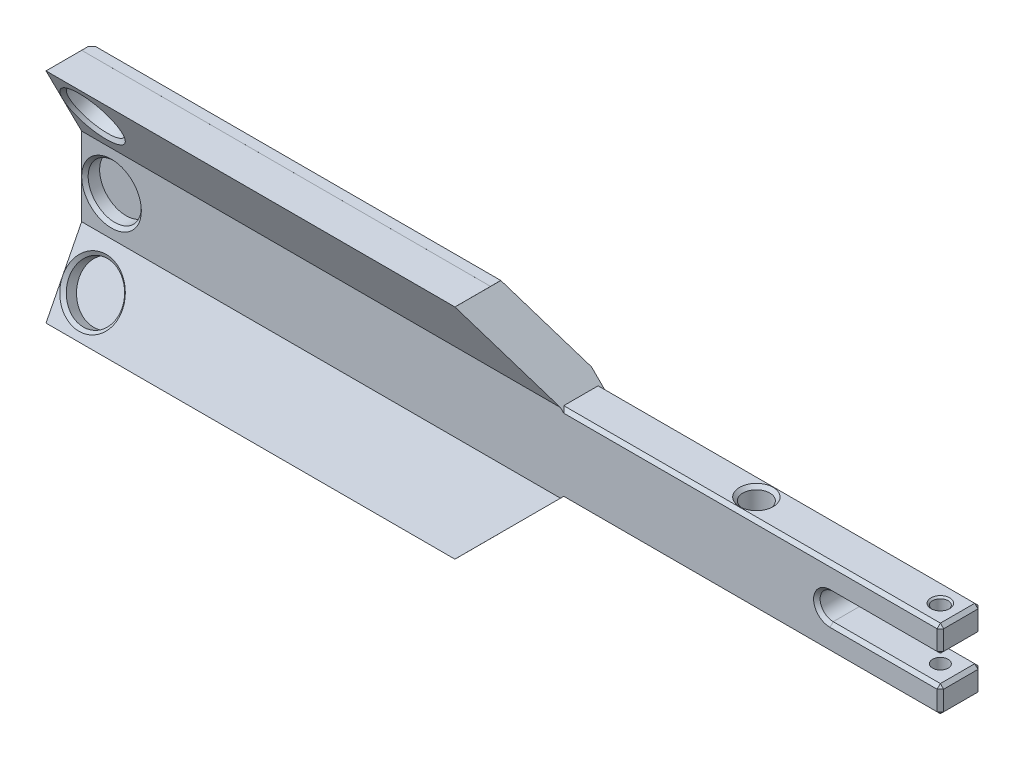
SolidWorks part; units mm, degrees
ref_plane "Front" through (0, 0, 0) normal (0, 0, 1) x (1, 0, 0)
ref_plane "Top" through (0, 0, 0) normal (0, 1, 0) x (1, 0, 0)
ref_plane "Right" through (0, 0, 0) normal (1, 0, 0) x (0, 0, -1)
sketch "Sketch1" plane through (0, 0, 0) normal (0, 0, 1) x (1, 0, 0)
  line L1 (52.5, -4.8) -> (-52.5, -4.8)
  line L2 (52.5, -4.8) -> (52.5, 4.8)
  line L3 (52.5, 4.8) -> (-52.5, 4.8)
  line L4 (-52.5, -4.8) -> (-52.5, 4.8)
  line L5 (52.5, -4.8) -> (-52.5, 4.8) construction
  line L6 (52.5, 4.8) -> (-52.5, -4.8) construction
  point P0 (0, 0)
  dimension "D1" = 9.6
  dimension "D2" = 105
extrude "Boss-Extrude1" add sketch "Sketch1" along normal blind 5
sketch "Sketch2" plane through (0, 4.8, 0) normal (0, 1, 0) x (1, 0, 0)
  line L0 (52.5, -5) -> (52.5, 0) construction
  line L2 (52.5, 0) -> (-52.5, 0) construction
  circle A0 centre (27.5, -2.5) radius 1.65
  dimension "D3" = 3.3
  dimension "D1" = 2.5
  dimension "D2" = 25
sketch "Sketch4" plane through (0, 0, 5) normal (0, 0, 1) x (1, 0, 0)
  line L0 (39, 0) -> (45, 0) construction
  line L1 (39, 1.6) -> (45, 1.6)
  line L2 (39, -1.6) -> (45, -1.6)
  arc A0 (39, 1.6) -> (39, -1.6) centre (39, 0) ccw
  arc A1 (45, -1.6) -> (45, 1.6) centre (45, 0) ccw
  point P2 (42, 0)
  dimension "D1" = 1.6
  dimension "D2" = 42
  dimension "D3" = 6
extrude "Cut-Extrude1" cut sketch "Sketch4" against normal blind 5
sketch "Sketch14" plane through (0, 0, 5) normal (0, 0, 1) x (1, 0, 0)
  line L0 (39, -1.6) -> (45, -1.6) construction
  line L1 (44.5, -1.6) -> (52.5, -1.6)
  line L2 (44.5, -1.6) -> (44.5, 1.6)
  line L3 (44.5, 1.6) -> (52.5, 1.6)
  line L4 (52.5, -1.6) -> (52.5, 1.6)
  line L5 (52.5, -4.8) -> (52.5, 4.8) construction
  line L6 (45, 1.6) -> (39, 1.6) construction
  dimension "D1" = 8
extrude "Cut-Extrude7" cut sketch "Sketch14" against normal blind 10
sketch "Sketch8" plane through (0, 0, 0) normal (0, 0, -1) x (-1, 0, 0)
  line L0 (52.5, 4.8) -> (52.5, -4.8) construction
  line L1 (52.5, 13.355) -> (2.5, 13.355)
  line L2 (52.5, 13.355) -> (52.5, -13.355)
  line L3 (52.5, -13.355) -> (2.5, -13.355)
  line L4 (2.5, 13.355) -> (2.5, -13.355)
  line L5 (2.5, 0) -> (52.5, 0) construction
  line L7 (-52.5, 0) -> (53.7381, 0) construction
  dimension "D1" = 26.71
  dimension "D3" = 50
extrude "Boss-Extrude3" add sketch "Sketch8" against normal up to surface (5 mm away) up to face at (22.675, 0, 5)
sketch "Sketch9" plane through (-52.5, 0, 0) normal (-1, 0, 0) x (0, 0, 1)
  line L0 (5, 13.355) -> (5, -13.355) construction
  line L1 (5, 13.3543) -> (9.357, 13.3543)
  line L2 (9.357, 13.3543) -> (5, 4.8)
  line L3 (5, 4.8) -> (5, 13.3543)
  line L4 (-3.9634, 0) -> (12.9509, 0) construction
  line L5 (9.357, -13.3543) -> (5, -4.8)
  line L6 (5, -13.3543) -> (9.357, -13.3543)
  line L7 (5, -4.8) -> (5, -13.3543)
  circle A0 centre (25, 0) radius 20 construction
  dimension "D1" = 40
  dimension "D2" = 9.6
  dimension "D3" = 9.6
extrude "Boss-Extrude4" add sketch "Sketch9" against normal up to surface (50 mm away) up to face at (-2.5, 9.0775, 2.5)
sketch "Sketch13" plane through (-52.5, 0, 0) normal (-1, 0, 0) x (0, 0, 1)
  line L0 (0, 6) -> (3.7462, 13.355)
  line L1 (0, 13.355) -> (0, -13.355) construction
  line L2 (5, 13.355) -> (0, 13.355) construction
  line L3 (3.7462, 13.355) -> (-2, 13.355)
  line L4 (-2, 13.355) -> (-2, -13.355)
  line L5 (-2, -13.355) -> (3.7462, -13.355)
  line L6 (5, -13.355) -> (0, -13.355) construction
  line L7 (3.7462, -13.355) -> (0, -6)
  line L8 (0, -6) -> (0, 6)
  line L10 (5, 4.8) -> (9.357, 13.3543) construction
  line L11 (9.357, -13.3543) -> (5, -4.8) construction
  dimension "D1" = 5
  dimension "D2" = 5
  dimension "D3" = 2
extrude "Cut-Extrude6" cut sketch "Sketch13" against normal through all
chamfer "Chamfer4" distance 8.55 2 edges at (-2.5, 4.8, 2.5) (-2.5, -4.8, 2.5)
sketch "Sketch10" plane through (-52.5, 0, 0) normal (-1, 0, 0) x (0, 0, 1)
  line L0 (5, 4.8) -> (5, -4.8) construction
  line L1 (5, 4.8) -> (9.357, 13.3543) construction
  line L2 (9.357, -13.3543) -> (5, -4.8) construction
  circle A0 centre (25, 0) radius 20
sketch "Sketch11" plane through (0, 0, 5) normal (0, 0, 1) x (1, 0, 0)
  line L2 (-52.5, 4.8) -> (-52.5, -4.8) construction
  circle A0 centre (-48.85, 0) radius 3.25
  dimension "D1" = 6.5
  dimension "D2" = 3.65
extrude "Cut-Extrude3" cut sketch "Sketch11" against normal blind 1.8
sketch "Sketch12" plane through (0, -1.0334, 2.0288) normal (0, -0.4539, 0.8911) x (1, 0, 0)
  line L1 (-2.5, 16.1464) -> (-52.5, 16.1464) construction
  line L2 (-52.5, 31.3464) -> (-52.5, -8.6536) construction
  circle A0 centre (-48.85, 11.6464) radius 3.25
  dimension "D1" = 6.5
  dimension "D2" = 4.5
  dimension "D3" = 3.65
extrude "Cut-Extrude4" cut sketch "Sketch12" against normal blind 1.8
mirror "Mirror2" about plane through (0, 0, 0) normal (0, 1, 0) of "Cut-Extrude4"
chamfer "Chamfer2" distance 0.4 angle 45 3 edges at (-45.6, 0, 5) (-48.85, -6.4485, 5.8396) (-48.85, 6.4485, 5.8396)
ref_plane "Plane1" through (-48.5, 0, 0) normal (-1, 0, 0) x (0, 0, 1)
extrude "Cut-Extrude5" cut sketch "Sketch2" against normal blind 10
chamfer "Chamfer5" distance 0.4 angle 45 20 edges at (25.85, -4.8, 2.5) (25.85, 4.8, 2.5) (52.5, 4.8, 2.5) (29.275, 4.8, 5) (52.5, -3.2, 5) (52.5, 3.2, 5) (29.275, -4.8, 5) (52.5, -4.8, 2.5) (29.275, 4.8, 0) (29.275, -4.8, 0) (52.5, 3.2, 0) (52.5, -3.2, 0) (45.75, -1.6, 0) (37.4, 0, 0) (45.75, 1.6, 0) (45.75, 1.6, 5) (37.4, 0, 5) (45.75, -1.6, 5) (52.5, 1.6, 2.5) (52.5, -1.6, 2.5)
chamfer "Chamfer6" distance 0.4 angle 45 3 edges at (-52.5, 9.6775, 1.8731) (-52.5, -9.6775, 1.8731) (-52.5, 0, 0)
sketch "Sketch15" plane through (0, -4.8, 0) normal (0, -1, 0) x (1, 0, 0)
  line L0 (52.5, 4.6) -> (52.5, 0.4) construction
  line L1 (52.1, 0) -> (6.45, 0) construction
  circle A0 centre (50, 2.5) radius 0.95
  dimension "D1" = 1.9
  dimension "D2" = 2.5
  dimension "D3" = 2.5
extrude "Cut-Extrude8" cut sketch "Sketch15" against normal blind 10
chamfer "Chamfer11" distance 0.2 angle 45 2 edges at (50.95, 4.8, 2.5) (50.95, -4.8, 2.5)
